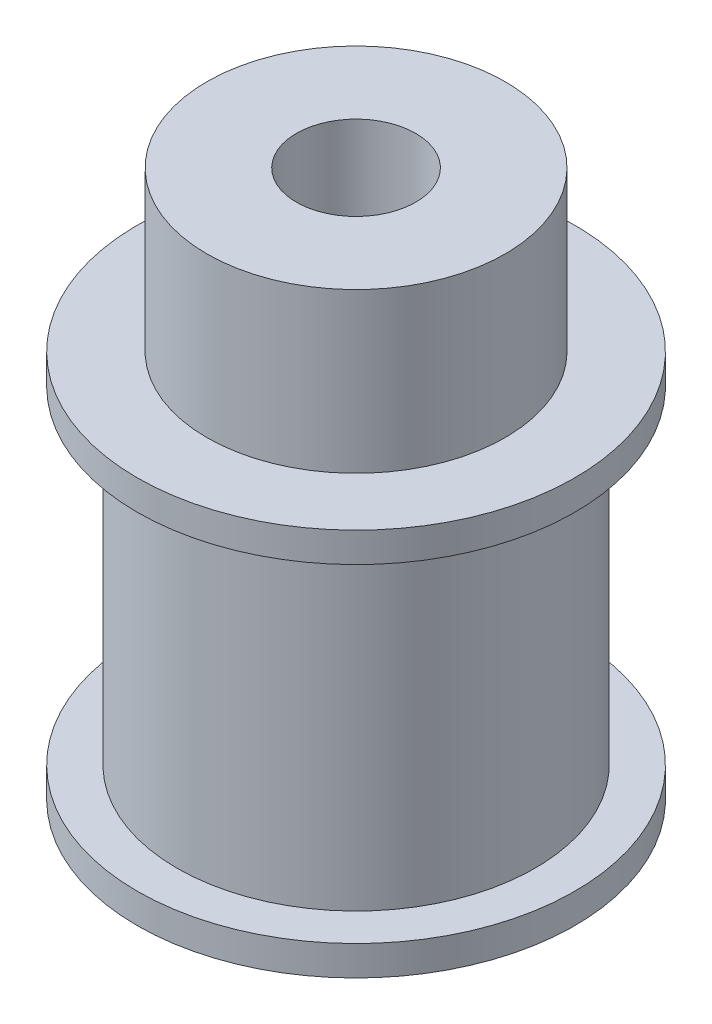
SolidWorks part; units mm, degrees
ref_plane "Front Plane" through (0, 0, 0) normal (0, 0, 1) x (1, 0, 0)
ref_plane "Top Plane" through (0, 0, 0) normal (0, 1, 0) x (1, 0, 0)
ref_plane "Right Plane" through (0, 0, 0) normal (1, 0, 0) x (0, 0, -1)
sketch "Sketch1" plane through (0, 0, 0) normal (0, 1, 0) x (1, 0, 0)
  circle A0 centre (0, 0) radius 11
  dimension "D1" = 22
extrude "Boss-Extrude1" add sketch "Sketch1" along normal blind 1.5
sketch "Sketch2" plane through (0, 1.5, 0) normal (0, 1, 0) x (1, 0, 0)
  circle A0 centre (0, 0) radius 9
  dimension "D1" = 18
extrude "Boss-Extrude2" add sketch "Sketch2" along normal blind 16.5
extrude "Boss-Extrude3" add sketch "Sketch1<2>" along normal blind 1.5 from surface starting at face at (0, 18, 9)
sketch "Sketch1<2>" plane through (0, 0, 0) normal (0, 1, 0) x (1, 0, 0) same geometry as "Sketch1"
sketch "Sketch3" plane through (0, 19.5, 0) normal (0, 1, 0) x (1, 0, 0)
  circle A0 centre (0, 0) radius 7.5
  dimension "D1" = 15
extrude "Boss-Extrude4" add sketch "Sketch3" along normal blind 8
sketch "Sketch4" plane through (0, 0, 0) normal (0, -1, 0) x (1, 0, 0)
  circle A0 centre (0, 0) radius 3
  dimension "D1" = 6
extrude "Cut-Extrude1" cut sketch "Sketch4" against normal through all
